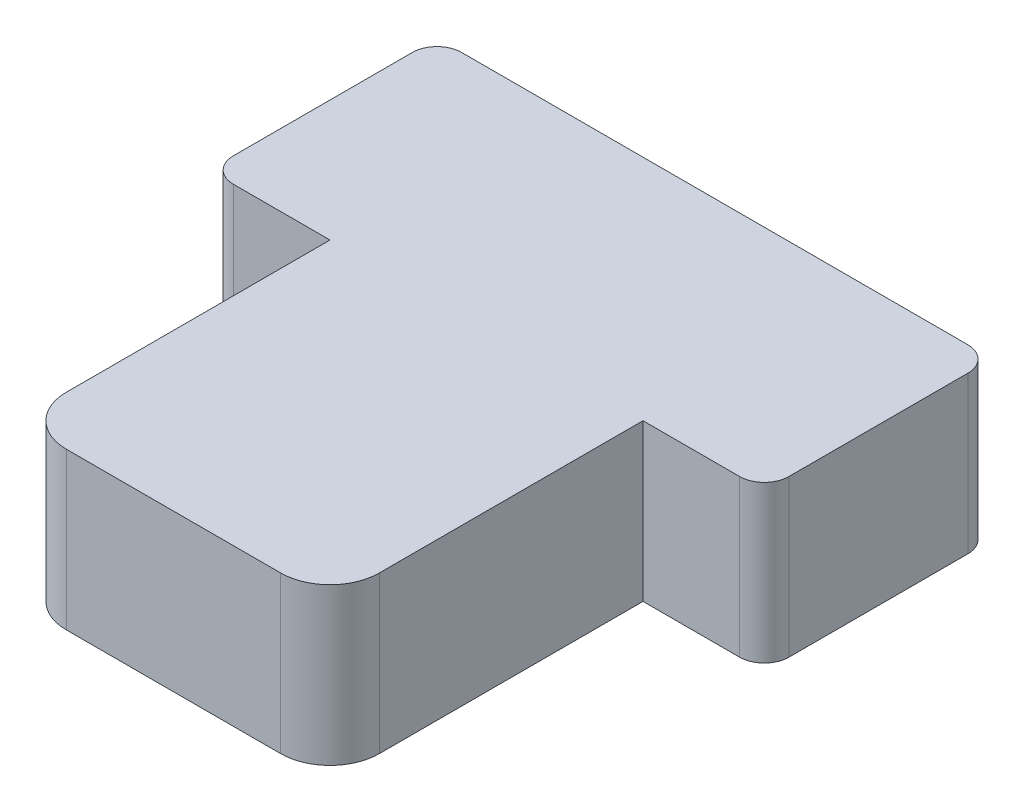
SolidWorks part; units mm, degrees
material "Beech"
ref_plane "Front Plane" through (0, 0, 0) normal (0, 0, 1) x (1, 0, 0)
ref_plane "Top Plane" through (0, 0, 0) normal (0, 1, 0) x (1, 0, 0)
ref_plane "Right Plane" through (0, 0, 0) normal (1, 0, 0) x (0, 0, -1)
sketch "Sketch1" plane through (0, 0, 0) normal (0, 1, 0) x (1, 0, 0)
  line L0 (0, 0) -> (6.35, 0)
  line L1 (0, 0) -> (0, 6.35)
  line L2 (6.35, 0) -> (6.35, 6.35)
  line L4 (-2.46, 10.9807) -> (-2.46, 6.35)
  line L5 (-2.46, 10.9807) -> (8.81, 10.9807)
  line L6 (-2.46, 6.35) -> (0, 6.35)
  line L7 (8.81, 10.9807) -> (8.81, 6.35)
  line L8 (6.35, 6.35) -> (8.81, 6.35)
  dimension "D1" = 6.35
  dimension "D2" = 6.35
  dimension "D3" = 11.27
  dimension "D4" = 4.6307
extrude "MotorSupport_Extrude" add sketch "Sketch1" along normal blind 3.175
fillet "MotorSupport_BottomFillet" radius 1 2 edges at (0, 1.5875, 0) (6.35, 1.5875, 0)
fillet "MotorSupport_TopFillet" radius 0.5 4 edges at (-2.46, 1.5875, -6.35) (-2.46, 1.5875, -10.9807) (8.81, 1.5875, -10.9807) (8.81, 1.5875, -6.35)
equation "\"CageLeftBottomEdge\"=22.11mm"
equation "\"CageLeftTopEdge\"=22.11mm"
equation "\"CageRightBottomEdge\"=21.63mm"
equation "\"CageRightTopEdge\"=21.63mm"
equation "\"CageHeight\"=86.04mm"
equation "\"CageLength\"=73.76mm"
equation "\"CageTopScrewClearance\"=10mm"
equation "\"CageBottomScrewClearance\"=25mm"
equation "\"CageLeftTopDepth\"= 11.65mm"
equation "\"CageLeftBottomDepth\"=11.11mm"
equation "\"CageLeftTopHeight\"=8.56175mm"
equation "\"CageLeftBottomHeight\"=16mm"
equation "\"CageRightTopDepth\"= 11.05mm"
equation "\"CageRightBottomDepth\"=10.58mm"
equation "\"CageRightTopHeight\"=9.6mm"
equation "\"CageRightBottomHeight\"=15.49mm"
equation "\"CageLeftTopChannelDepth\"=2.41908mm"
equation "\"CageLeftBottomChannelDepth\"=2.588mm"
equation "\"CageLeftChannelHeight\"=11.7mm"
equation "\"CageRightTopChannelDepth\"=2.32mm"
equation "\"CageRightBottomChannelDepth\"=2.318mm"
equation "\"CageRightChannelHeight\"=10mm"
equation "\"CageChanRelHeight\"=23.99mm"
equation "\"CageChanRelDepth\"=5.492mm"
equation "\"CageChamberRadius\"=16.261mm"
equation "\"CageScrewDiameter\"=4.8mm"
equation "\"CageSetScrewDiameter\"=3.5mm"
equation "\"CageAxleRadius\"=6.639mm"
equation "\"CageAxleKeyHeight\"=1.619mm"
equation "\"CageAxleKeyWidth\"=2.662mm"
equation "\"CageHoseWindowWidth\"=16.29mm"
equation "\"CageHoseWindowHeight\"=26.5mm"
equation "\"CageHoseWindow-Edge\"=8.89mm"
equation "\"CageScrew-VerticalEdge\"=5.0mm"
equation "\"CageScrew-HorizontalEdge\"=7.5mm"
equation "\"CageScrew-HoseCornerScrewEdge\"=4.45mm"
equation "\"CageAxle-BottomEdge\"=56.05mm"
equation "\"CageAxle-FrontEdge\"=46.03mm"
equation "\"CageBackSetScrew-Axle\"=40mm"
equation "\"CageFrontSetScrew-Axle\"=22mm"
equation "\"CageVelocityWindow-BackEdge\"=34.8mm"
equation "\"CageVelocityWindow-BottomEdge\"=27.55mm"
equation "\"CageVelocityWindowHeight\"=22.29mm"
equation "\"CageVelocityWindowWidth\"=12.61mm"
equation "\"TriggerSlot-BottomEdge\"=6.35mm"
equation "\"TriggerSlot-FrontEdge\"=15mm"
equation "\"TriggerSlotSize\"=6.7mm"
equation "\"TriggerRackOffset\"=.236224in"
equation "\"TriggerSlotSizeInt\"=.25in"
equation "\"MotorMountLegLength\"=.25in"
equation "\"GearOffset\"=.264907in"
equation "\"TriggerSlotSpacing\"=.25in"
equation "\"TGMGearFaceDiameter\"=24.40mm"
equation "\"TGMCylinderLength\"=15.00mm"
equation "\"TGMScrewHole-Center\"=8.70mm"
equation "\"TGMScrewHoleDiameter\"=5.04mm"
equation "\"TGMCenterHoleDiameter\"=9.50mm"
equation "\"TGMShaftCollarSideLength\"=19.00mm"
equation "\"TGMShaftCollarDockingDepth\"=7.00mm"
equation "\"whitemotordepth\"=11.27mm"
equation "\"whitemotorbackdepth\"=3.845mm"
equation "\"whitemotoraxledepth\" = 3.5mm"
equation "\"whitemotoraxleoffset\"=11.4mm"
equation "\"whitemotorwidth\"=12.07mm"
equation "\"whitemotorheight\"=16.68mm"
equation "\"whitemotorcylinderlength\" =13.04mm"
equation "\"whitemotorcylinderradius\"=3.845mm"
equation "\"whitemotorcylinderoffset\"=2.35mm"
equation "\"whitemotorcutoutlength\"=1.88mm"
equation "\"whitemotorouterrad\"=5mm"
equation "\"whitemotorinnerrad\"=2.95mm"
equation "\"D1@Sketch1\"=\"TriggerSlotSizeInt\""
equation "\"D2@Sketch1\"=\"MotorMountLegLength\""
equation "\"D3@Sketch1\"=\"whitemotordepth\""
equation "\"D4@Sketch1\"=\"GearOffset\"+\"TriggerRackOffset\"-\"whitemotoraxleoffset\"+\"elasticdepth\"+.005in"
equation "\"D1@MotorSupport_Extrude\"=.125in"
equation "\"TriggerMiniSlotWidth\"=3.5mm"
equation "\"TriggerRackWidth\"=6.5mm"
equation "\"elasticracklength\"=2in"
equation "\"elasticrackpegsize\"=.25in"
equation "\"elasticrackpegbuffer\"=.125in"
equation "\"elasticrackpegspacing\"=1.76476378in"
equation "\"elasticbaybuffer\"=.25in"
equation "\"elasticdepth\"=.125in"
equation "\"elasticbaydepth\"=.75in"
equation "\"motormountwidth\"=12mm"
equation "\"motormountcornerfillet\"=3mm"
